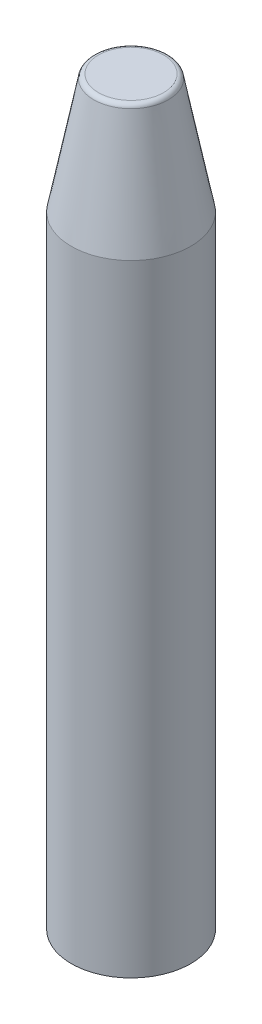
SolidWorks part; units mm, degrees
ref_plane "Alzado" through (0, 0, 0) normal (0, 0, 1) x (1, 0, 0)
ref_plane "Planta" through (0, 0, 0) normal (0, 1, 0) x (1, 0, 0)
ref_plane "Vista lateral" through (0, 0, 0) normal (1, 0, 0) x (0, 0, -1)
sketch "Croquis1" plane through (0, 0, 0) normal (0, 1, 0) x (1, 0, 0)
  circle A0 centre (0, 0) radius 2.5
  dimension "D1" = 5
extrude "Saliente-Extruir1" add sketch "Croquis1" along normal blind 26
sketch "Croquis2" plane through (0, 26, 0) normal (0, 1, 0) x (1, 0, 0)
  circle A1 centre (0, 0) radius 2.5
  circle A2 centre (0, 0) radius 2.5
  dimension "D1" = 0
extrude "Saliente-Extruir2" add sketch "Croquis2" along normal blind 5 draft 11
fillet "Redondeo1" radius 0.2 1 edges at (0, 31, 1.5281)
sketch "Croquis5" plane through (0, 0, 0) normal (0, -1, 0) x (1, 0, 0)
  circle A0 centre (0, 0) radius 1.5
  dimension "D1" = 3
extrude "Cortar-Extruir1" cut sketch "Croquis5" against normal blind 9
thread "Rosca1" pitch 0.5 method extrude profile "Perfil de rosca1" start angle 0, offset 2, length 8, pitch 0.5, diameter 3
ref_plane "Plano1" through (1.5, -2, 0) normal (0, 0, 1) x (1, 0, 0)
sketch "Perfil de rosca1" plane through (1.5, -2, 0) normal (0, 0, 1) x (1, 0, 0)
  line L0 (0, 0) -> (0, 0.5) construction
  line L11 (0, 0) -> (0, 0.4375)
  line L12 (0, 0.4375) -> (-0.2706, 0.2812)
  line L13 (-0.2706, 0.2812) -> (-0.2706, 0.1562)
  line L15 (-0.2706, 0.1562) -> (0, 0)
  line L17 (-0.2706, 0.2187) -> (0, 0.2187) construction
  point P2 (0, 0)
  dimension "Pitch" = 0.5
  dimension "Profile_Angle" = 60
  dimension "Profile_Land" = 0.125
  dimension "Profile_Height" = 0.2706
sketch "Croquis8" plane through (0, 0, 0) normal (0, -1, 0) x (1, 0, 0)
  circle A0 centre (0, 0) radius 3
extrude "Cortar-Extruir2" cut sketch "Croquis8" along normal blind 9
